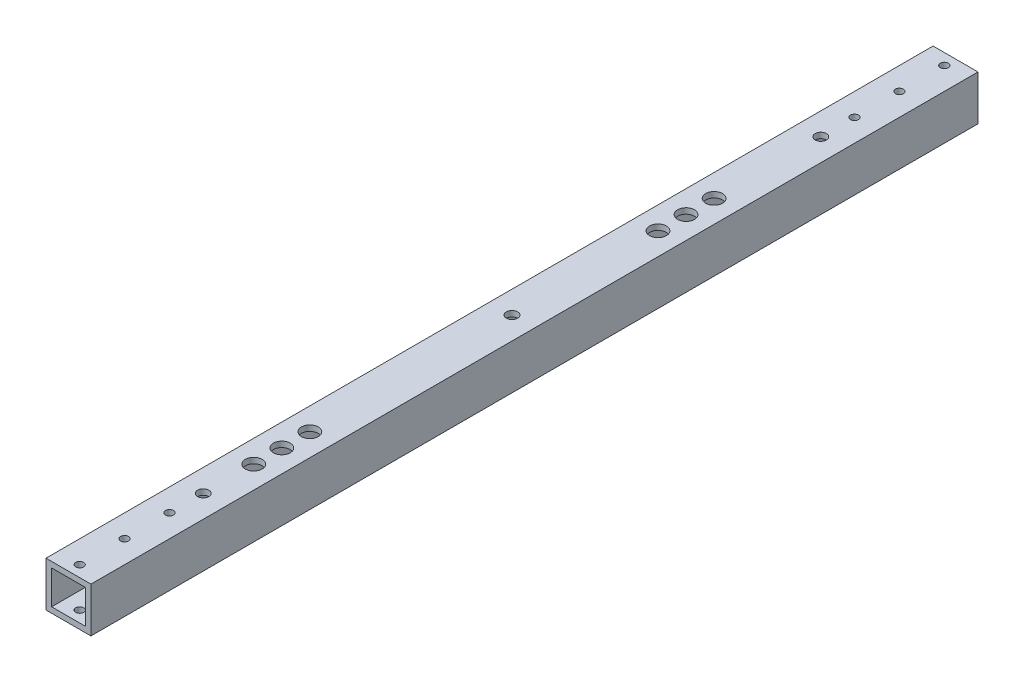
SolidWorks part; units mm, degrees
material "6061-T6 (SS)"
ref_plane "Front Plane" through (0, 0, 0) normal (0, 0, 1) x (1, 0, 0)
ref_plane "Top Plane" through (0, 0, 0) normal (0, 1, 0) x (1, 0, 0)
ref_plane "Right Plane" through (0, 0, 0) normal (1, 0, 0) x (0, 0, -1)
sketch "Sketch1" plane through (0, 0, 0) normal (0, 0, 1) x (1, 0, 0)
  line L1 (-12.7, -12.7) -> (12.7, -12.7)
  line L2 (-12.7, -12.7) -> (-12.7, 12.7)
  line L3 (-12.7, 12.7) -> (12.7, 12.7)
  line L4 (12.7, -12.7) -> (12.7, 12.7)
  line L5 (-12.7, -12.7) -> (12.7, 12.7) construction
  line L6 (-12.7, 12.7) -> (12.7, -12.7) construction
  point P0 (0, 0)
  dimension "D1" = 25.4
  dimension "D2" = 25.4
extrude "Extrude-Thin1" add sketch "Sketch1" along normal blind 501.65 thin thin type one direction reverse wall 3.175
hole_wizard "#8 Clearance Hole1" positions "3DSketch1" profile "Sketch3" hole size "#8" standard "ANSI Inch" end condition through all
sketch3d "3DSketch1"
  line L1 (12.7, 12.7, 0) -> (-12.7, 12.7, 0) construction
  line L6 (0, 12.7, 501.65) -> (0, 12.7, 0) construction
  line L7 (12.7, 12.7, 501.65) -> (-12.7, 12.7, 501.65) construction
  point P57 (0, 12.7, 6.35)
  point P59 (0, 12.7, 31.75)
  point P61 (0, 12.7, 57.15)
  point P63 (0, 12.7, 469.9)
  point P65 (0, 12.7, 444.5)
  point P67 (0, 12.7, 495.3)
  dimension "D1" = 25.4
  dimension "D2" = 25.4
  dimension "D3" = 6.35
  dimension "D4" = 25.4
  dimension "D5" = 25.4
  dimension "D6" = 6.35
sketch "Sketch3" plane through (0, 12.7, 495.3) normal (1, 0, 0) x (0, 0, 1)
  line L0 (0, 0) -> (0, 25.4)
  line L1 (0, 25.4) -> (2.2479, 25.4)
  line L2 (2.2479, 25.4) -> (2.2479, 0)
  line L5 (2.2479, 0) -> (0, 0)
  line L11 (0, -6.35) -> (0, 107.95) construction
  dimension "Thru Hole Dia." = 4.4958
  dimension "Thru Hole Depth" = 25.4
hole_wizard "1/4 (0.25) Diameter Hole1" positions "Sketch10" profile "Sketch11" hole size "1/4" standard "ANSI Inch"
sketch "Sketch10" plane through (381, 12.7, 250.825) normal (0, 1, 0) x (1, 0, 0)
  line L0 (-381, 174.625) -> (-381, -174.625) construction
  line L2 (-381, 174.625) -> (-381, 250.825) construction
  line L5 (-381, -174.625) -> (-381, -250.825) construction
  point P0 (-381, 174.625)
  point P2 (-381, 0)
  point P4 (-381, -174.625)
  point P26 (0, 0)
  point P31 (0, 0)
sketch "Sketch11" plane through (0, 12.7, 76.2) normal (1, 0, 0) x (0, 0, 1)
  line L0 (0, 0) -> (0, 30.4827)
  line L1 (0, 30.4827) -> (3.175, 28.575)
  line L2 (3.175, 28.575) -> (3.175, 0)
  line L3 (3.175, 0) -> (0, 0)
  line L4 (0, 30.4827) -> (-3.175, 28.575) construction
  line L5 (0, -6.35) -> (0, 107.95) construction
  dimension "Hole Dia." = 6.35
  dimension "Hole Depth" = 28.575
  dimension "Drill Angle" = 118
hole_wizard "3/8 (0.375) Diameter Hole2" positions "Sketch14" profile "Sketch15" hole size "3/8" standard "ANSI Inch" end condition through all
sketch "Sketch14" plane through (381, 12.7, 250.825) normal (0, 1, 0) x (1, 0, 0)
  point P9 (-92.583, 346.075)
  point P12 (-35.433, 346.075)
  point P18 (35.814, 346.075)
  point P21 (92.964, 346.075)
  point P24 (-22.9616, -346.775)
  point P27 (50.0634, -346.775)
  point P30 (123.0884, -346.775)
  point P33 (-381, 114.3)
  point P36 (-381, 98.425)
  point P39 (-381, 82.55)
  point P42 (-381, -114.3)
  point P45 (-381, -130.175)
  point P48 (-381, -146.05)
sketch "Sketch15" plane through (288.417, 12.7, -95.25) normal (1, 0, 0) x (0, 0, 1)
  line L0 (0, 0) -> (0, 25.4)
  line L1 (0, 25.4) -> (4.7625, 25.4)
  line L2 (4.7625, 25.4) -> (4.7625, 0)
  line L3 (4.7625, 0) -> (0, 0)
  line L4 (0, -6.35) -> (0, 107.95) construction
  dimension "Thru Hole Dia." = 9.525
  dimension "Thru Hole Depth" = 25.4
